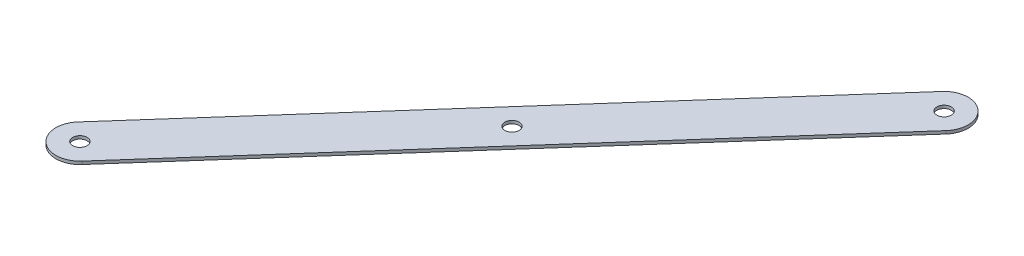
SolidWorks part; units mm, degrees
ref_plane "Front" through (0, 0, 0) normal (0, 0, 1) x (1, 0, 0)
ref_plane "Top" through (0, 0, 0) normal (0, 1, 0) x (1, 0, 0)
ref_plane "Right" through (0, 0, 0) normal (1, 0, 0) x (0, 0, -1)
sketch "Sketch1" plane through (0, 0, 0) normal (0, 1, 0) x (1, 0, 0)
  line L0 (0, 0) -> (214.595, 242.5445) construction
  line L1 (-9.5115, 8.4155) -> (205.0834, 250.96)
  line L2 (9.5115, -8.4155) -> (224.1065, 234.129)
  arc A0 (-9.5115, 8.4155) -> (9.5115, -8.4155) centre (0, 0) ccw
  arc A1 (224.1065, 234.129) -> (205.0834, 250.96) centre (214.595, 242.5445) ccw
  circle A2 centre (107.2975, 121.2722) radius 3.81
  circle A3 centre (214.595, 242.5445) radius 3.81
  circle A4 centre (0, 0) radius 3.81
  point P3 (107.2975, 121.2722)
  dimension "D3" = 7.62
  dimension "D4" = 7.62
  dimension "D5" = 7.62
  dimension "D1" = 323.85
  dimension "D2" = 25.4
extrude "Boss-Extrude1" add sketch "Sketch1" along normal blind 1.5875
